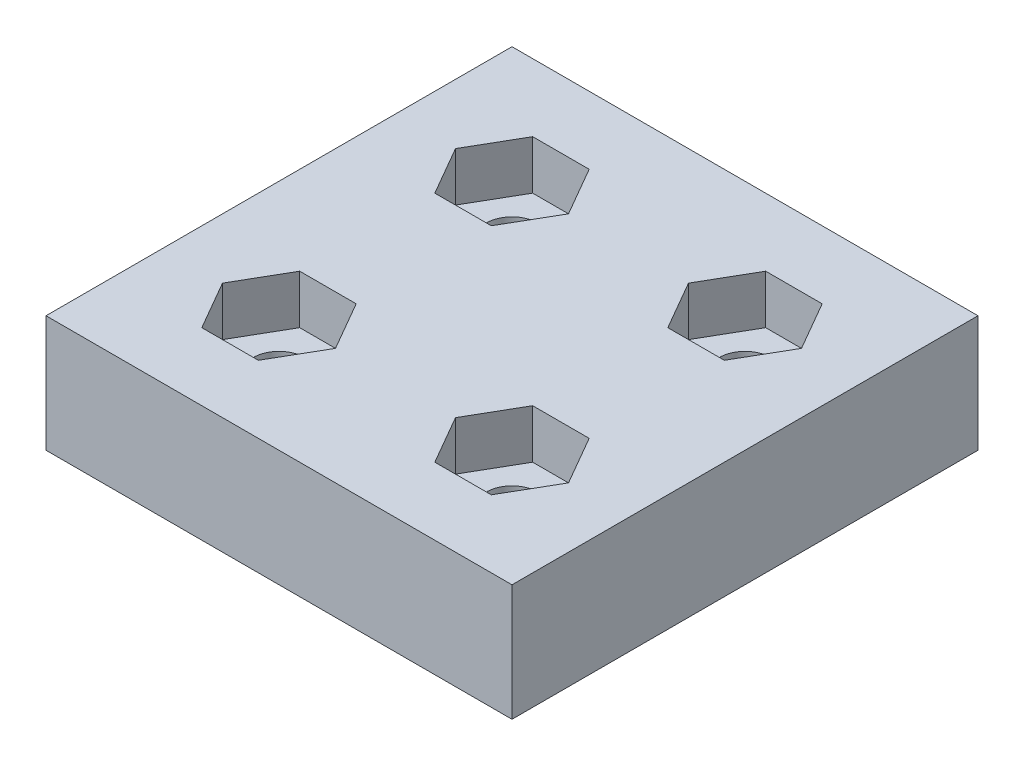
SolidWorks part; units mm, degrees
ref_plane "Front Plane" through (0, 0, 0) normal (0, 0, 1) x (1, 0, 0)
ref_plane "Top Plane" through (0, 0, 0) normal (0, 1, 0) x (1, 0, 0)
ref_plane "Right Plane" through (0, 0, 0) normal (1, 0, 0) x (0, 0, -1)
sketch "Sketch1" plane through (0, 0, 0) normal (0, 1, 0) x (1, 0, 0)
  line L1 (0, 0) -> (40, 0)
  line L2 (0, 0) -> (0, 40)
  line L3 (0, 40) -> (40, 40)
  line L4 (40, 0) -> (40, 40)
  circle A0 centre (10, 30) radius 2.2
  circle A1 centre (30, 30) radius 2.2
  circle A2 centre (30, 10) radius 2.2
  circle A3 centre (10, 10) radius 2.2
  dimension "D11" = 4.4
  dimension "D12" = 4.4
  dimension "D13" = 4.4
  dimension "D14" = 4.4
  dimension "D1" = 40
  dimension "D2" = 40
  dimension "D3" = 10
  dimension "D4" = 10
  dimension "D5" = 10
  dimension "D6" = 10
  dimension "D7" = 10
  dimension "D8" = 10
  dimension "D9" = 10
  dimension "D10" = 10
extrude "Boss-Extrude1" add sketch "Sketch1" along normal blind 10
sketch "Sketch2" plane through (0, 10, 0) normal (0, 1, 0) x (1, 0, 0)
  line L0 (10, 10) -> (30, 10) construction
  line L1 (30, 10) -> (30, 30) construction
  line L2 (30, 30) -> (10, 30) construction
  line L3 (10, 30) -> (10, 10) construction
  line L5 (14.8497, 10) -> (12.4249, 14.2)
  line L6 (12.4249, 14.2) -> (7.5751, 14.2)
  line L7 (7.5751, 14.2) -> (5.1503, 10)
  line L8 (5.1503, 10) -> (7.5751, 5.8)
  line L9 (7.5751, 5.8) -> (12.4249, 5.8)
  line L10 (12.4249, 5.8) -> (14.8497, 10)
  line L11 (25.1503, 10) -> (27.5751, 5.8)
  line L12 (27.5751, 5.8) -> (32.4249, 5.8)
  line L13 (32.4249, 5.8) -> (34.8497, 10)
  line L14 (34.8497, 10) -> (32.4249, 14.2)
  line L15 (32.4249, 14.2) -> (27.5751, 14.2)
  line L16 (27.5751, 14.2) -> (25.1503, 10)
  line L17 (25.1503, 30) -> (27.5751, 25.8)
  line L18 (27.5751, 25.8) -> (32.4249, 25.8)
  line L19 (32.4249, 25.8) -> (34.8497, 30)
  line L20 (34.8497, 30) -> (32.4249, 34.2)
  line L21 (32.4249, 34.2) -> (27.5751, 34.2)
  line L22 (27.5751, 34.2) -> (25.1503, 30)
  line L23 (14.8497, 30) -> (12.4249, 34.2)
  line L24 (12.4249, 34.2) -> (7.5751, 34.2)
  line L25 (7.5751, 34.2) -> (5.1503, 30)
  line L26 (5.1503, 30) -> (7.5751, 25.8)
  line L27 (7.5751, 25.8) -> (12.4249, 25.8)
  line L28 (12.4249, 25.8) -> (14.8497, 30)
  circle A0 centre (10, 10) radius 4.2 construction
  circle A1 centre (30, 10) radius 4.2 construction
  circle A2 centre (30, 30) radius 4.2 construction
  circle A3 centre (10, 30) radius 4.2 construction
  dimension "D1" = 8.4
  dimension "D2" = 8.4
  dimension "D3" = 8.4
  dimension "D4" = 8.4
extrude "Cut-Extrude1" cut sketch "Sketch2" against normal blind 4.2
equation "\"hSpacing\"=10"
equation "\"D3@Sketch1\"=\"hSpacing\""
equation "\"D5@Sketch1\"=\"hSpacing\""
equation "\"D6@Sketch1\"=\"hSpacing\""
equation "\"D4@Sketch1\"=\"hSpacing\""
equation "\"D7@Sketch1\"=\"hSpacing\""
equation "\"D8@Sketch1\"=\"hSpacing\""
equation "\"D9@Sketch1\"=\"hSpacing\""
equation "\"D10@Sketch1\"=\"hSpacing\""
equation "\"hDiam\"=4.4"
equation "\"D11@Sketch1\"=\"hDiam\""
equation "\"D12@Sketch1\"=\"hDiam\""
equation "\"D13@Sketch1\"=\"hDiam\""
equation "\"D14@Sketch1\"=\"hDiam\""
equation "\"nutFlat\"=8.4"
equation "\"D1@Sketch2\"=\"nutFlat\""
equation "\"D2@Sketch2\"=\"nutFlat\""
equation "\"D3@Sketch2\"=\"nutFlat\""
equation "\"D4@Sketch2\"=\"nutFlat\""
